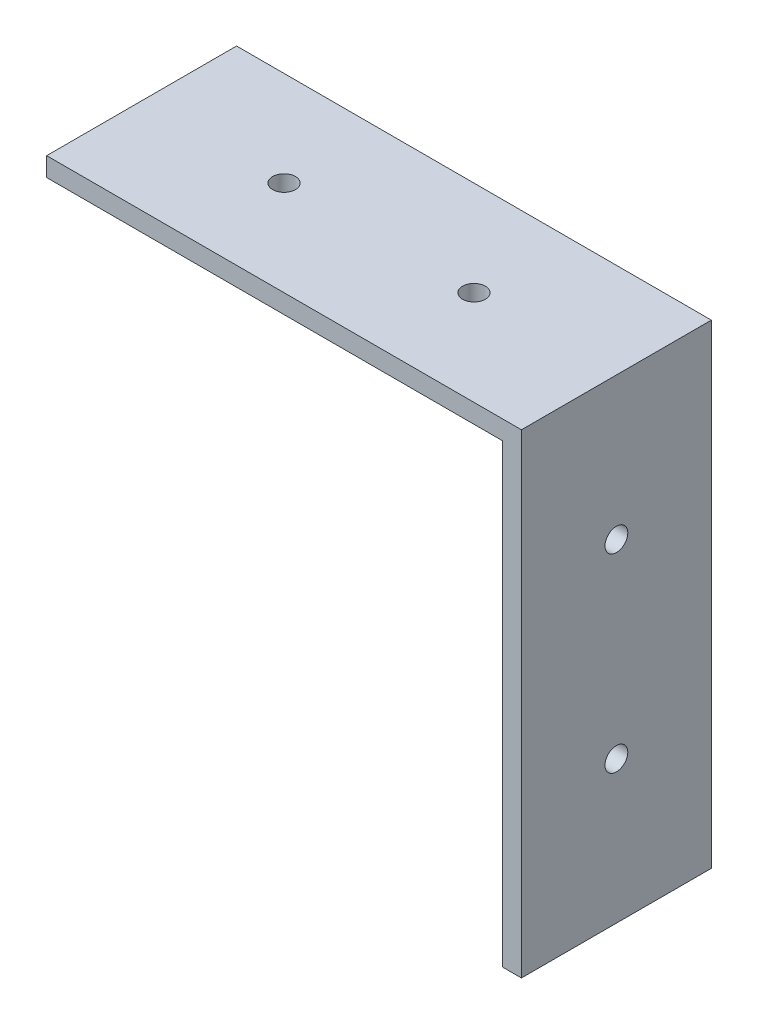
SolidWorks part; units mm, degrees
ref_plane "Front Plane" through (0, 0, 0) normal (0, 0, 1) x (1, 0, 0)
ref_plane "Top Plane" through (0, 0, 0) normal (0, 1, 0) x (1, 0, 0)
ref_plane "Right Plane" through (0, 0, 0) normal (1, 0, 0) x (0, 0, -1)
sketch "Sketch1" plane through (0, 0, 0) normal (0, 0, 1) x (1, 0, 0)
  line L0 (-50, 0) -> (-50, -2)
  line L1 (-50, -2) -> (-2, -2)
  line L2 (-2, -2) -> (-2, -50)
  line L3 (-2, -50) -> (0, -50)
  line L4 (0, -50) -> (0, 0)
  line L5 (0, 0) -> (-50, 0)
  point P3 (0, 0)
  dimension "D1" = 2
  dimension "D2" = 50
extrude "Boss-Extrude1" add sketch "Sketch1" along normal blind 20
sketch "Sketch2" plane through (0, 0, 0) normal (0, 1, 0) x (1, 0, 0)
  line L0 (0, -20) -> (0, 0) construction
  point P0 (-35, -10)
  point P1 (-15, -10)
  point P4 (0, 0)
  point P5 (-15, -8.9213)
  point P6 (0, 0)
  point P7 (-47.7773, -15)
  point P8 (0, 0)
  point P9 (0, 0)
  point P11 (0, 0)
  point P15 (0, 0)
  point P16 (0, -10)
  dimension "D1" = 15
  dimension "D3" = 20
sketch "Sketch3" plane through (0, 0, 0) normal (1, 0, 0) x (0, 0, -1)
  line L0 (-20, 0) -> (0, 0) construction
  point P0 (-10, -15)
  point P1 (-10, -35)
  point P4 (0, 0)
  point P5 (-10, 0)
  point P6 (-14.4757, -36.4534)
  point P8 (0, 0)
  point P9 (0, 0)
  dimension "D1" = 15
  dimension "D2" = 20
hole_wizard "M2 Clearance Hole1" positions "3DSketch1" profile "Sketch5" hole size "M2" standard "ANSI Metric"
sketch3d "3DSketch1"
  point P0 (-35, 0, 10)
  point P3 (-15, 0, 10)
  point P7 (0, -15, 10)
  point P10 (0, -35, 10)
sketch "Sketch5" plane through (-35, 0, 10) normal (1, 0, 0) x (0, 0, 1)
  line L0 (0, 0) -> (0, 3.721)
  line L1 (0, 3.721) -> (1.2, 3)
  line L2 (1.2, 3) -> (1.2, 0)
  line L5 (1.2, 0) -> (0, 0)
  line L10 (0, 3.721) -> (-1.2, 3) construction
  line L11 (0, -6.35) -> (0, 107.95) construction
  dimension "Hole Dia." = 2.4
  dimension "Hole Depth" = 3
  dimension "Drill Angle" = 118
